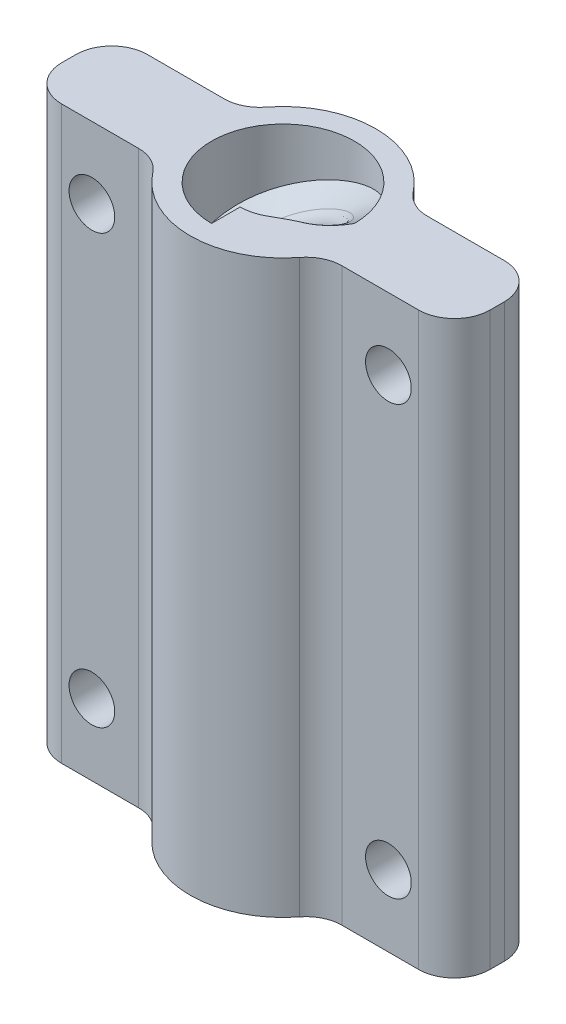
SolidWorks part; units mm, degrees
ref_plane "Front Plane" through (0, 0, 0) normal (0, 0, 1) x (1, 0, 0)
ref_plane "Top Plane" through (0, 0, 0) normal (0, 1, 0) x (1, 0, 0)
ref_plane "Right Plane" through (0, 0, 0) normal (1, 0, 0) x (0, 0, -1)
sketch "Sketch1" plane through (0, 0, 0) normal (0, 1, 0) x (1, 0, 0)
  line L1 (-15, -3) -> (15, -3)
  line L2 (-15, -3) -> (-15, 3)
  line L3 (-15, 3) -> (15, 3)
  line L4 (15, -3) -> (15, 3)
  line L5 (-15, -3) -> (15, 3) construction
  line L6 (-15, 3) -> (15, -3) construction
  point P0 (0, 0)
  dimension "D1" = 6
  dimension "D2" = 30
extrude "Boss-Extrude1" add sketch "Sketch1" along normal mid plane 40
sketch "Sketch2" plane through (0, 20, 0) normal (0, 1, 0) x (1, 0, 0)
  circle A0 centre (0, 0) radius 6.5
  dimension "D1" = 13
extrude "Boss-Extrude2" add sketch "Sketch2" against normal up to surface (40 mm away) up to face at (0, -20, 0)
sketch "Sketch3" plane through (0, 0, -3) normal (0, 0, -1) x (-1, 0, 0)
  line L0 (27.7888, 0) -> (-27.7888, 0) construction
  line L3 (-15, -15) -> (-5.7663, -15) construction
  line L4 (-15, 20) -> (-15, -20) construction
  line L5 (-5.7663, -20) -> (-5.7663, 20) construction
  line L6 (-15, 15) -> (-5.7663, 15) construction
  circle A0 centre (-10.3831, 15) radius 1.6
  circle A1 centre (-10.3831, -15) radius 1.6
  point P3 (0, 0)
  point P14 (-10.3831, -15)
  point P15 (-10.3831, 15)
  point P18 (0, 0)
  dimension "D2" = 3.2
  dimension "D1" = 30
extrude "Cut-Extrude1" cut sketch "Sketch3" against normal through all
mirror "Mirror1" about plane through (0, 0, 0) normal (1, 0, 0) of "Cut-Extrude1"
sketch "Sketch4" plane through (0, 20, 0) normal (0, 1, 0) x (1, 0, 0)
  circle A0 centre (0, 0) radius 5
  dimension "D1" = 10
extrude "Cut-Extrude2" cut sketch "Sketch4" against normal through all
sketch "Sketch5" plane through (0, 20, 0) normal (0, 1, 0) x (1, 0, 0)
  circle A0 centre (0, 0) radius 5 construction
  circle A1 centre (0, 0) radius 5
curve "Helix/Spiral1" pitch 10 height 40 radius 5 left hand yes centre (0, 20, 0) axis (0, -1, 0) start towards (0, 0, 1)
sketch "Sketch6" plane through (0, 0, 0) normal (1, 0, 0) x (0, 0, -1)
  line L0 (-5, 22.5) -> (-5, 17.5)
  line L2 (-5, 17.5) -> (-3.5, 18.366)
  line L3 (-3, 19.2321) -> (-3, 20.7679)
  line L4 (-3.5, 21.634) -> (-5, 22.5)
  arc A0 (-3.5, 18.366) -> (-3, 19.2321) centre (-4, 19.2321) ccw
  arc A1 (-3, 20.7679) -> (-3.5, 21.634) centre (-4, 20.7679) ccw
  point P4 (-5, 20)
  dimension "D4" = 1
  dimension "D1" = 60
  dimension "D2" = 2
  dimension "D3" = 5
sweep "Sweep1" add profiles "Sketch6" path "Helix/Spiral1"
sketch "Sketch7" plane through (0, -20, 0) normal (0, -1, 0) x (1, 0, 0)
  line L1 (26.2702, 13.0944) -> (-26.2702, 13.0944)
  line L2 (26.2702, 13.0944) -> (26.2702, -13.0944)
  line L3 (26.2702, -13.0944) -> (-26.2702, -13.0944)
  line L4 (-26.2702, 13.0944) -> (-26.2702, -13.0944)
  line L5 (26.2702, 13.0944) -> (-26.2702, -13.0944) construction
  line L6 (26.2702, -13.0944) -> (-26.2702, 13.0944) construction
  point P0 (0, 0)
extrude "Cut-Extrude3" cut sketch "Sketch7" along normal through all
sketch "Sketch8" plane through (0, 20, 0) normal (0, 1, 0) x (1, 0, 0)
  line L1 (-34.8339, 17.9765) -> (34.8339, 17.9765)
  line L2 (-34.8339, 17.9765) -> (-34.8339, -17.9765)
  line L3 (-34.8339, -17.9765) -> (34.8339, -17.9765)
  line L4 (34.8339, 17.9765) -> (34.8339, -17.9765)
  line L5 (-34.8339, 17.9765) -> (34.8339, -17.9765) construction
  line L6 (-34.8339, -17.9765) -> (34.8339, 17.9765) construction
  point P0 (0, 0)
extrude "Cut-Extrude4" cut sketch "Sketch8" along normal through all
fillet "Fillet1" radius 2.5 4 edges at (5.7663, 0, -3) (-5.7663, 0, -3) (-5.7663, 0, 3) (5.7663, 0, 3)
fillet "Fillet2" radius 2.5 4 edges at (-15, 0, -3) (15, 0, -3) (15, 0, 3) (-15, 0, 3)
